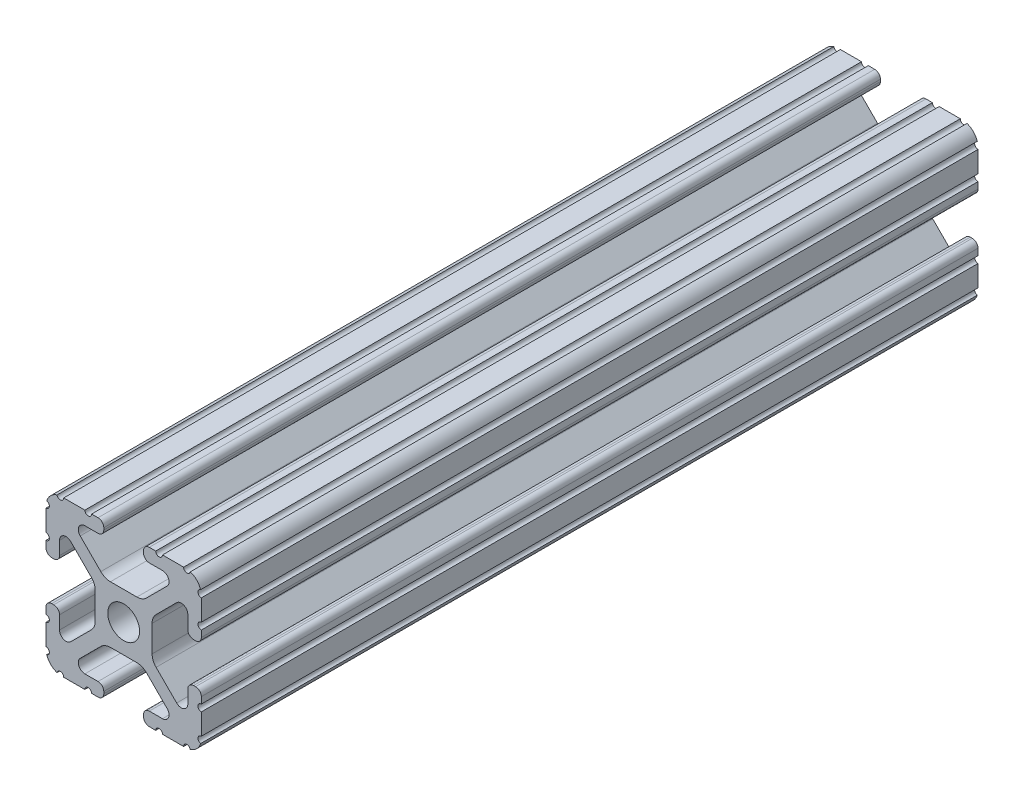
SolidWorks part; units mm, degrees
ref_plane "Front Plane" through (0, 0, 0) normal (0, 0, 1) x (1, 0, 0)
ref_plane "Top Plane" through (0, 0, 0) normal (0, 1, 0) x (1, 0, 0)
ref_plane "Right Plane" through (0, 0, 0) normal (1, 0, 0) x (0, 0, -1)
sketch "Sketch2" plane through (0, 0, 0) normal (0, 0, 1) x (1, 0, 0)
  line L0 (0, 12.7) -> (0, -12.7) construction
  line L1 (-12.7, 0) -> (12.7, 0) construction
  line L2 (3.2512, -12.7) -> (12.7, -12.7)
  line L3 (12.7, -12.7) -> (12.7, -3.2512)
  line L4 (3.2512, -12.7) -> (3.2512, -10.4902)
  line L5 (3.2512, -10.4902) -> (8.9276, -10.4902)
  line L6 (8.9276, -10.4902) -> (3.0856, -4.6482)
  line L7 (0, 0) -> (12.7, -12.7) construction
  line L8 (12.7, -3.2512) -> (10.4902, -3.2512)
  line L9 (10.4902, -3.2512) -> (10.4902, -8.9276)
  line L10 (10.4902, -8.9276) -> (4.6482, -3.0856)
  circle A0 centre (0, 0) radius 2.6035
  arc A1 (6.3485, -10.4902) -> (7.1039, -8.6665) centre (6.3485, -9.4219) ccw construction
  point P8 (0, -4.6482)
  dimension "Center Hole Diameter" = 5.207
  dimension "Rail Height" = 25.4
  dimension "Rail Width" = 25.4
  dimension "T-Slot Width" = 6.5024
  dimension "Slot Inner Width" = 14.8336
  dimension "Thickness" = 2.2098
  dimension "Slot Depth" = 5.842
  dimension "D1" = 2.2098
sketch "Sketch3" plane through (0, 0, 0) normal (1, 0, 0) x (0, 0, -1)
  line L0 (-63.5, -12.7) -> (63.5, -12.7) construction
  line L1 (-38.1, 0) -> (38.1, 0) construction
  line L3 (63.5, 0) -> (-63.5, 0) construction
sketch "Sketch4" plane through (0, 0, 0) normal (0, 0, 1) x (1, 0, 0)
  line L0 (4.1904, -12.7) -> (10.1173, -12.7)
  line L1 (3.2512, -12.7) -> (12.7, -12.7) construction
  line L2 (3.2512, -12.7) -> (3.2512, -10.4902) construction
  line L3 (3.2512, -10.4902) -> (8.9276, -10.4902) construction
  line L4 (3.2512, -11.4294) -> (3.2512, -11.7608)
  line L5 (4.1904, -10.4902) -> (6.3485, -10.4902)
  line L6 (0, -4.6482) -> (2.164, -4.6482)
  line L7 (8.9276, -10.4902) -> (3.0856, -4.6482) construction
  line L8 (3.7373, -5.2999) -> (7.1039, -8.6665)
  line L9 (12.7, -12.7) -> (12.7, -3.2512) construction
  line L10 (10.4902, -8.9276) -> (4.6482, -3.0856) construction
  line L11 (10.4902, -3.2512) -> (10.4902, -8.9276) construction
  line L12 (10.4902, -6.3485) -> (10.4902, -4.1904)
  line L13 (12.7, -3.2512) -> (10.4902, -3.2512) construction
  line L14 (11.4294, -3.2512) -> (11.7608, -3.2512)
  line L15 (12.7, -4.1904) -> (12.7, -10.1173)
  line L16 (8.6665, -7.1039) -> (5.2999, -3.7373)
  line L17 (4.6482, 0) -> (4.6482, -2.164)
  line L18 (-12.7, 0) -> (12.7, 0) construction
  line L19 (0, -4.6482) -> (0, -2.6035)
  line L20 (0, 12.7) -> (0, -12.7) construction
  line L21 (4.6482, 0) -> (2.6035, 0)
  arc A0 (3.2512, -11.7608) -> (4.1904, -12.7) centre (4.1904, -11.7608) ccw
  arc A2 (3.2512, -11.4294) -> (4.1904, -10.4902) centre (4.1904, -11.4294) cw
  arc A3 (6.3485, -10.4902) -> (7.1039, -8.6665) centre (6.3485, -9.4219) ccw
  arc A4 (2.164, -4.6482) -> (3.7373, -5.2999) centre (2.164, -6.8732) cw
  arc A5 (10.1173, -12.7) -> (12.7, -10.1173) centre (10.1173, -10.1173) ccw
  arc A6 (8.6665, -7.1039) -> (10.4902, -6.3485) centre (9.4219, -6.3485) ccw
  arc A7 (10.4902, -4.1904) -> (11.4294, -3.2512) centre (11.4294, -4.1904) cw
  arc A8 (11.7608, -3.2512) -> (12.7, -4.1904) centre (11.7608, -4.1904) cw
  arc A9 (5.2999, -3.7373) -> (4.6482, -2.164) centre (6.8732, -2.164) cw
  circle A10 centre (0, 0) radius 2.6035 construction
  arc A11 (0, -2.6035) -> (2.6035, 0) centre (0, 0) ccw
  dimension "D1" = 2.5827
  dimension "D2" = 2.225
  dimension "D3" = 0.9392
extrude "Boss-Extrude1" add sketch "Sketch4" along normal up to vertex (63.5 mm away) from vertex up to point (0, -12.7, 63.5) starting at point (0, -12.7, -63.5)
sketch "Sketch5" plane through (0, 0, 0) normal (0, 0, 1) x (1, 0, 0)
  line L0 (3.2512, -12.7) -> (12.7, -12.7) construction
  line L1 (4.1904, -10.4902) -> (6.3485, -10.4902) construction
  line L3 (0, 0) -> (12.7, -12.7) construction
  line L4 (6.3485, -10.4902) -> (6.3485, -12.7) construction
  line L5 (8.9276, -10.4902) -> (3.0856, -4.6482) construction
  circle A0 centre (10.3562, -12.7) radius 0.5524
  circle A1 centre (5.796, -12.7) radius 0.5524
  circle A2 centre (12.7, -10.3562) radius 0.5524
  circle A3 centre (12.7, -5.796) radius 0.5524
  point P10 (5.2694, -10.4902)
  point P12 (9.4219, -6.3485)
  dimension "D1" = 1.1049
extrude "Cut-Extrude1" cut sketch "Sketch5" against normal through all both and the other way through all
mirror "Mirror1" about plane through (0, 0, 0) normal (1, 0, 0) of bodies 137 134
mirror "Mirror2" about plane through (0, 0, 0) normal (0, 1, 0) of bodies 135
equation "\"D1@Sketch2\"=\"Thickness@Sketch2\""
equation "\"D2@Sketch4\"=\"Slot Inner Width@Sketch2\"*0.15"
equation "\"D1@Sketch4\"=\"D3@Sketch4\"*2.75"
equation "\"D3@Sketch4\"=\"Thickness@Sketch2\"*0.425"
equation "\"D1@Sketch5\"=\"Thickness@Sketch2\"*0.5"
equation "\"D1@Boss-Extrude1\"=\"Length@Sketch3\""
